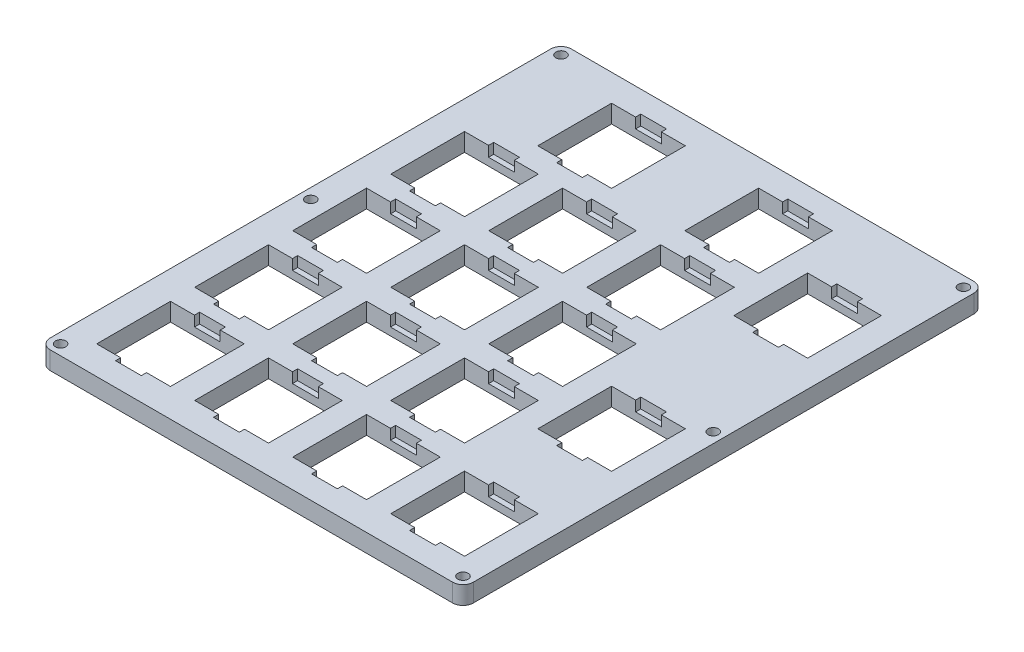
SolidWorks part; units mm, degrees
ref_plane "Plan de face" through (0, 0, 0) normal (0, 0, 1) x (1, 0, 0)
ref_plane "Plan de dessus" through (0, 0, 0) normal (0, 1, 0) x (1, 0, 0)
ref_plane "Plan de droite" through (0, 0, 0) normal (1, 0, 0) x (0, 0, -1)
sketch "Esquisse1" plane through (0, 0, 0) normal (0, 1, 0) x (1, 0, 0)
  line L1 (-38, -47.5) -> (38, -47.5)
  line L2 (-38, -47.5) -> (-38, 47.5)
  line L3 (-38, 47.5) -> (38, 47.5)
  line L4 (38, -47.5) -> (38, 47.5)
  line L5 (-38, -47.5) -> (38, 47.5) construction
  line L6 (-38, 47.5) -> (38, -47.5) construction
  point P0 (0, 0)
  dimension "D1" = 76
  dimension "D2" = 95
extrude "Boss.-Extru.1" add sketch "Esquisse1" along normal blind 3.5
sketch "Esquisse2" plane through (0, 0, 0) normal (0, -1, 0) x (1, 0, 0)
  line L1 (-35.5, 45) -> (-21.2, 45)
  line L2 (-35.5, 45) -> (-35.5, 30.7)
  line L3 (-35.5, 30.7) -> (-21.2, 30.7)
  line L4 (-21.2, 45) -> (-21.2, 30.7)
  dimension "D1" = 14.3
  dimension "D2" = 14.3
extrude "Enlèv. mat.-Extru.1" cut sketch "Esquisse2" against normal blind 3.5
sketch "Esquisse3" plane through (0, 0, 0) normal (0, -1, 0) x (1, 0, 0)
  line L0 (-21.2, 45) -> (-35.5, 45) construction
  line L1 (-30.85, 46) -> (-25.85, 46)
  line L2 (-30.85, 46) -> (-30.85, 44)
  line L3 (-30.85, 44) -> (-25.85, 44)
  line L4 (-25.85, 46) -> (-25.85, 44)
  line L5 (-30.85, 46) -> (-25.85, 44) construction
  line L6 (-30.85, 44) -> (-25.85, 46) construction
  line L7 (-35.5, 30.7) -> (-21.2, 30.7) construction
  line L8 (-30.85, 31.7) -> (-25.85, 31.7)
  line L9 (-30.85, 31.7) -> (-30.85, 29.7)
  line L10 (-30.85, 29.7) -> (-25.85, 29.7)
  line L11 (-25.85, 31.7) -> (-25.85, 29.7)
  line L12 (-30.85, 31.7) -> (-25.85, 29.7) construction
  line L13 (-30.85, 29.7) -> (-25.85, 31.7) construction
  point P0 (-28.35, 45)
  point P7 (-28.35, 30.7)
  dimension "D1" = 5
  dimension "D2" = 5
  dimension "D3" = 2
  dimension "D4" = 2
extrude "Enlèv. mat.-Extru.2" cut sketch "Esquisse3" against normal blind 2 from offset 1.5 offset against normal yes
pattern_linear "Répétition linéaire1" count 3 spacing 19 along (1, 0, 0) count 4 spacing 19 along (0, 0, -1) of "Enlèv. mat.-Extru.2", "Enlèv. mat.-Extru.1"
pattern_linear "Répétition linéaire2" count 4 spacing 19 along (1, 0, 0) of "Enlèv. mat.-Extru.1", "Enlèv. mat.-Extru.2"
sketch "Esquisse4" plane through (0, 0, 0) normal (0, -1, 0) x (1, 0, 0)
  line L1 (2.5, -31) -> (16.8, -31)
  line L2 (2.5, -31) -> (2.5, -45.3)
  line L3 (2.5, -45.3) -> (16.8, -45.3)
  line L4 (16.8, -31) -> (16.8, -45.3)
  line L5 (-26, -31) -> (-11.7, -31)
  line L6 (-26, -31) -> (-26, -45.3)
  line L7 (-26, -45.3) -> (-11.7, -45.3)
  line L8 (-11.7, -31) -> (-11.7, -45.3)
  line L9 (21.5, -21.5) -> (35.8, -21.5)
  line L10 (21.5, -21.5) -> (21.5, -35.8)
  line L11 (21.5, -35.8) -> (35.8, -35.8)
  line L12 (35.8, -21.5) -> (35.8, -35.8)
  line L13 (21.5, 16.5) -> (35.8, 16.5)
  line L14 (21.5, 16.5) -> (21.5, 2.2)
  line L15 (21.5, 2.2) -> (35.8, 2.2)
  line L16 (35.8, 16.5) -> (35.8, 2.2)
  point P16 (0, 0)
  point P17 (0, 0)
  point P18 (0, 0)
  dimension "D1" = 14.3
  dimension "D2" = 14.3
  dimension "D3" = 14.3
  dimension "D4" = 14.3
  dimension "D5" = 14.3
  dimension "D6" = 14.3
  dimension "D7" = 14.3
  dimension "D8" = 14.3
  dimension "D9" = 14.3
extrude "Enlèv. mat.-Extru.3" cut sketch "Esquisse4" against normal blind 3.5
sketch "Esquisse5" plane through (0, 0, 0) normal (0, -1, 0) x (1, 0, 0)
  line L0 (35.8, 16.5) -> (21.5, 16.5) construction
  line L1 (26.15, 17.5) -> (31.15, 17.5)
  line L2 (26.15, 17.5) -> (26.15, 15.5)
  line L3 (26.15, 15.5) -> (31.15, 15.5)
  line L4 (31.15, 17.5) -> (31.15, 15.5)
  line L5 (26.15, 17.5) -> (31.15, 15.5) construction
  line L6 (26.15, 15.5) -> (31.15, 17.5) construction
  line L7 (21.5, 2.2) -> (35.8, 2.2) construction
  line L8 (26.15, 3.2) -> (31.15, 3.2)
  line L9 (26.15, 3.2) -> (26.15, 1.2)
  line L10 (26.15, 1.2) -> (31.15, 1.2)
  line L11 (31.15, 3.2) -> (31.15, 1.2)
  line L12 (26.15, 3.2) -> (31.15, 1.2) construction
  line L13 (26.15, 1.2) -> (31.15, 3.2) construction
  line L14 (35.8, -21.5) -> (21.5, -21.5) construction
  line L15 (26.15, -20.5) -> (31.15, -20.5)
  line L16 (26.15, -20.5) -> (26.15, -22.5)
  line L17 (26.15, -22.5) -> (31.15, -22.5)
  line L18 (31.15, -20.5) -> (31.15, -22.5)
  line L19 (26.15, -20.5) -> (31.15, -22.5) construction
  line L20 (26.15, -22.5) -> (31.15, -20.5) construction
  line L21 (21.5, -35.8) -> (35.8, -35.8) construction
  line L22 (26.15, -34.8) -> (31.15, -34.8)
  line L23 (26.15, -34.8) -> (26.15, -36.8)
  line L24 (26.15, -36.8) -> (31.15, -36.8)
  line L25 (31.15, -34.8) -> (31.15, -36.8)
  line L26 (26.15, -34.8) -> (31.15, -36.8) construction
  line L27 (26.15, -36.8) -> (31.15, -34.8) construction
  line L28 (16.8, -31) -> (2.5, -31) construction
  line L29 (7.15, -30) -> (12.15, -30)
  line L30 (7.15, -30) -> (7.15, -32)
  line L31 (7.15, -32) -> (12.15, -32)
  line L32 (12.15, -30) -> (12.15, -32)
  line L33 (7.15, -30) -> (12.15, -32) construction
  line L34 (7.15, -32) -> (12.15, -30) construction
  line L35 (2.5, -45.3) -> (16.8, -45.3) construction
  line L36 (7.15, -44.3) -> (12.15, -44.3)
  line L37 (7.15, -44.3) -> (7.15, -46.3)
  line L38 (7.15, -46.3) -> (12.15, -46.3)
  line L39 (12.15, -44.3) -> (12.15, -46.3)
  line L40 (7.15, -44.3) -> (12.15, -46.3) construction
  line L41 (7.15, -46.3) -> (12.15, -44.3) construction
  line L42 (-11.7, -31) -> (-26, -31) construction
  line L43 (-21.35, -30) -> (-16.35, -30)
  line L44 (-21.35, -30) -> (-21.35, -32)
  line L45 (-21.35, -32) -> (-16.35, -32)
  line L46 (-16.35, -30) -> (-16.35, -32)
  line L47 (-21.35, -30) -> (-16.35, -32) construction
  line L48 (-21.35, -32) -> (-16.35, -30) construction
  line L49 (-26, -45.3) -> (-11.7, -45.3) construction
  line L50 (-21.35, -44.3) -> (-16.35, -44.3)
  line L51 (-21.35, -44.3) -> (-21.35, -46.3)
  line L52 (-21.35, -46.3) -> (-16.35, -46.3)
  line L53 (-16.35, -44.3) -> (-16.35, -46.3)
  line L54 (-21.35, -44.3) -> (-16.35, -46.3) construction
  line L55 (-21.35, -46.3) -> (-16.35, -44.3) construction
  point P0 (28.65, 16.5)
  point P7 (28.65, 2.2)
  point P14 (28.65, -21.5)
  point P21 (28.65, -35.8)
  point P28 (9.65, -31)
  point P35 (9.65, -45.3)
  point P42 (-18.85, -31)
  point P49 (-18.85, -45.3)
  dimension "D1" = 2
  dimension "D2" = 2
  dimension "D3" = 2
  dimension "D4" = 2
  dimension "D5" = 2
  dimension "D6" = 2
  dimension "D7" = 2
  dimension "D8" = 2
  dimension "D9" = 5
  dimension "D10" = 5
  dimension "D11" = 5
  dimension "D12" = 5
  dimension "D13" = 5
  dimension "D14" = 5
  dimension "D15" = 5
  dimension "D16" = 5
extrude "Enlèv. mat.-Extru.4" cut sketch "Esquisse5" against normal blind 2 from offset 1.5 offset against normal yes
sketch "Esquisse6" plane through (0, 3.5, 0) normal (0, 1, 0) x (1, 0, 0)
  line L0 (38, -47.5) -> (38, 47.5) construction
  line L1 (-38, 47.5) -> (38, 47.5)
  line L2 (-38, 47.5) -> (-38, -47.5)
  line L3 (-38, -47.5) -> (38, -47.5)
  line L8 (38, 47.5) -> (38, -47.5)
  line L9 (-38, -47.5) -> (38, -47.5) construction
  line L10 (-41, 50.5) -> (-41, -50.5)
  line L11 (-41, -50.5) -> (41, -50.5)
  line L20 (41, 50.5) -> (41, -50.5)
  line L21 (-41, 50.5) -> (41, 50.5)
  dimension "D1" = 3
extrude "Boss.-Extru.2" add sketch "Esquisse6" against normal blind 3.5 contours L8 L1 L2 L3 | L10 L11 L20 L21 region at (0, 3.5, 0)
fillet "Congé1" radius 2 4 edges at (-41, 1.75, 50.5) (-41, 1.75, -50.5) (41, 1.75, -50.5) (41, 1.75, 50.5)
sketch "Esquisse7" plane through (0, 3.5, 0) normal (0, 1, 0) x (1, 0, 0)
  circle A0 centre (-39, 48.5) radius 1
  circle A1 centre (39, 48.5) radius 1
  circle A2 centre (-39, -48.5) radius 1
  circle A3 centre (39, -48.5) radius 1
  circle A4 centre (-39, 0) radius 1
  circle A5 centre (39, 0) radius 1
  dimension "D1" = 2
  dimension "D2" = 2
  dimension "D3" = 2
  dimension "D4" = 2
  dimension "D5" = 2
  dimension "D6" = 2
extrude "Enlèv. mat.-Extru.5" cut sketch "Esquisse7" against normal blind 3.5
chamfer "Chanfrein2" distance 1 angle 45 6 edges at (39, 0, -47.5) (-39, 0, -47.5) (39, 0, 1) (-39, 0, 1) (39, 0, 49.5) (-39, 0, 49.5)
